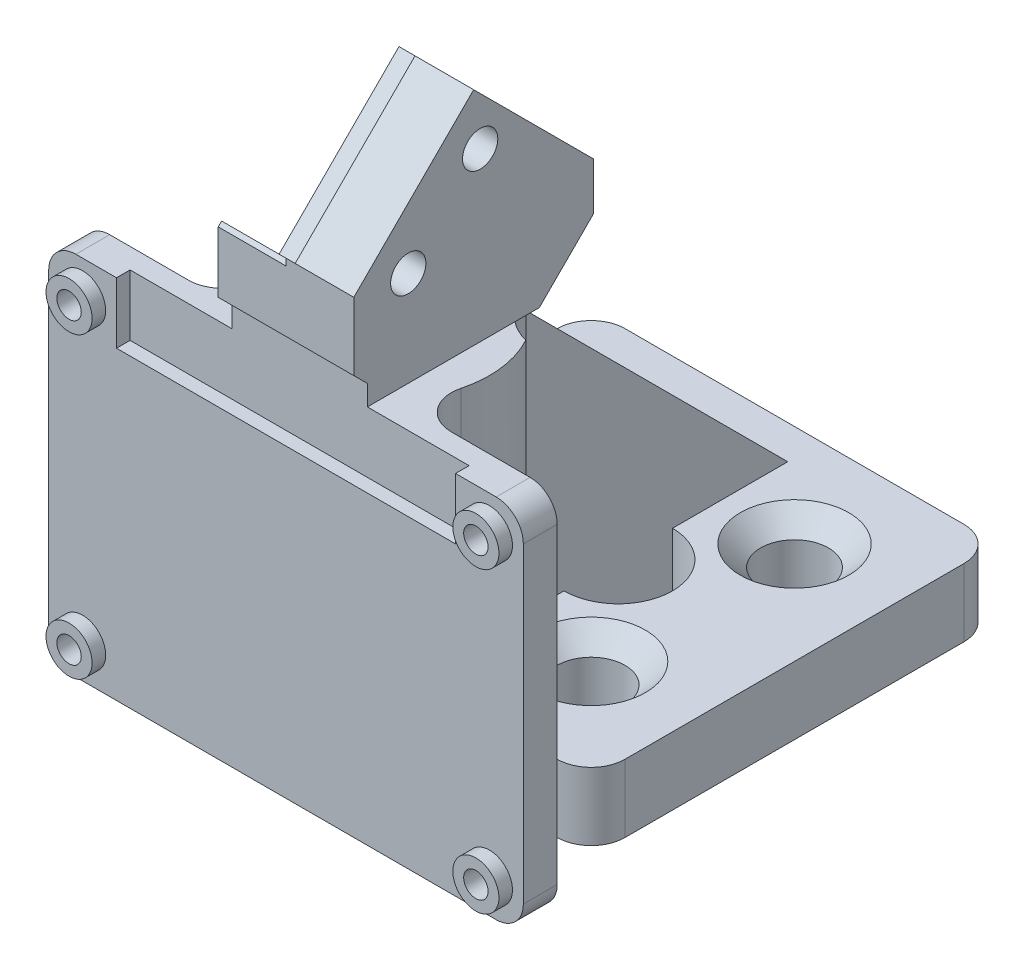
SolidWorks part; units mm, degrees
ref_plane "Front Plane" through (0, 0, 0) normal (0, 0, 1) x (1, 0, 0)
ref_plane "Top Plane" through (0, 0, 0) normal (0, 1, 0) x (1, 0, 0)
ref_plane "Right Plane" through (0, 0, 0) normal (1, 0, 0) x (0, 0, -1)
sketch "Sketch1" plane through (0, 0, 0) normal (0, 1, 0) x (1, 0, 0)
  circle A0 centre (0, 0) radius 15
  dimension "D1" = 30
extrude "Boss-Extrude1" add sketch "Sketch1" along normal blind 54
sketch "Sketch2" plane through (0, 0, 0) normal (1, 0, 0) x (0, 0, -1)
  line L0 (15, 54) -> (-15, 54) construction
  line L1 (-15, 54) -> (20.3553, 54)
  line L2 (-15, 54) -> (-15, 69)
  line L4 (20.3553, 54) -> (20.3553, 69)
  line L5 (-15, 69) -> (2.6777, 86.6777)
  line L6 (2.6777, 86.6777) -> (20.3553, 69)
  point P6 (0, 100)
  dimension "D1" = 25
  dimension "D2" = 15
  dimension "D3" = 15
  dimension "D4" = 45
  dimension "D5" = 15
extrude "Boss-Extrude2" add sketch "Sketch2" along normal mid plane 20
sketch "Sketch4" plane through (0, 42, 42) normal (0, 0.7071, 0.7071) x (1, 0, 0)
  line L0 (10, 38.1838) -> (-10, 38.1838) construction
  line L1 (-12.7, 38.1838) -> (0, 38.1838)
  line L2 (-12.7, 38.1838) -> (-12.7, 63.1838)
  line L3 (-12.7, 63.1838) -> (0, 63.1838)
  line L4 (0, 38.1838) -> (0, 63.1838)
  line L5 (10, 63.1838) -> (-10, 63.1838) construction
  dimension "D1" = 12.7
extrude "Cut-Extrude2" cut sketch "Sketch4" against normal blind 12.7
chamfer "Chamfer1" distance 1 angle 45 1 edges at (-5, 69, 15) first distance on face at (0, 61.5, 15)
sketch "Sketch5" plane through (0, 0, 0) normal (0, -1, 0) x (1, 0, 0)
  circle A0 centre (0, 0) radius 75
  dimension "D1" = 150
sketch "Sketch6" plane through (10, 0, 0) normal (1, 0, 0) x (0, 0, -1)
  line L0 (2.6777, 86.6777) -> (-15, 69) construction
  line L1 (20.3553, 69) -> (2.6777, 86.6777) construction
  line L2 (3.6323, 78.652) -> (-6.9743, 68.0454) construction
  circle A0 centre (3.6323, 78.652) radius 2.6
  circle A1 centre (-6.9743, 68.0454) radius 2.6
  dimension "D4" = 5.2
  dimension "D1" = 6.35
  dimension "D2" = 15
  dimension "D3" = 5
extrude "Cut-Extrude3" cut sketch "Sketch6" against normal through all
sketch "Sketch7" plane through (0, 0, 15) normal (0, 0, 1) x (1, 0, 0)
  line L0 (-31, 0) -> (31, 0)
  line L1 (-35, 4) -> (-35, 50)
  line L2 (-31, 54) -> (31, 54)
  line L3 (35, 4) -> (35, 50)
  line L4 (10, 54) -> (0, 54) construction
  circle A0 centre (-30, 49) radius 1.8
  circle A1 centre (30, 49) radius 1.8
  circle A2 centre (30, 5) radius 1.8
  circle A3 centre (-30, 5) radius 1.8
  arc A4 (31, 54) -> (35, 50) centre (31, 50) cw
  arc A5 (31, 0) -> (35, 4) centre (31, 4) ccw
  arc A6 (-31, 0) -> (-35, 4) centre (-31, 4) cw
  arc A7 (-35, 50) -> (-31, 54) centre (-31, 50) cw
  circle A8 centre (0, 27) radius 5 construction
  point P4 (30, 5)
  point P5 (30, 49)
  point P6 (-30, 49)
  point P7 (-30, 5)
  dimension "D1" = 3.6
  dimension "D2" = 10
  dimension "D3" = 4
  dimension "D4" = 65
  dimension "D5" = 30
  dimension "D6" = 30
  dimension "D7" = 5
  dimension "D8" = 49
  dimension "D9" = 22
  dimension "D10" = 22
  dimension "D11" = 5
extrude "Boss-Extrude4" add sketch "Sketch7" against normal blind 5
fillet "Fillet1" radius 5 2 edges at (-11.1803, 27, 10) (11.1803, 27, 10)
sketch "Sketch8" plane through (0, 0, 0) normal (0, -1, 0) x (1, 0, 0)
  line L1 (30, 0) -> (-30, 0)
  line L2 (30, 0) -> (30, -60)
  line L3 (30, -60) -> (-30, -60)
  line L4 (-30, 0) -> (-30, -60)
  point P4 (0, 0)
  dimension "D1" = 60
  dimension "D2" = 60
extrude "Boss-Extrude5" add sketch "Sketch8" against normal blind 10
sketch "Sketch9" plane through (0, 0, 0) normal (1, 0, 0) x (0, 0, -1)
  line L0 (15, 50) -> (55, 10)
  line L1 (15, 10) -> (15, 54) construction
  line L2 (60, 10) -> (0, 10) construction
  line L3 (15, 50) -> (10, 50)
  line L4 (10, 50) -> (10, 10)
  line L5 (10, 10) -> (55, 10)
  dimension "D1" = 45
  dimension "D2" = 5
  dimension "D3" = 40
extrude "Boss-Extrude6" add sketch "Sketch9" along normal mid plane 8
fillet "Fillet2" radius 5 4 edges at (-30, 5, -60) (30, 5, -60) (-30, 5, 0) (30, 5, 0)
sketch "Sketch10" plane through (0, 10, 0) normal (0, 1, 0) x (1, 0, 0)
  line L0 (-25, 60) -> (25, 60) construction
  line L1 (-15, 45) -> (15, 45) construction
  line L2 (-15, 45) -> (-15, 15) construction
  line L3 (-15, 15) -> (15, 15) construction
  line L4 (15, 45) -> (15, 15) construction
  line L5 (-15, 45) -> (15, 15) construction
  line L6 (-15, 15) -> (15, 45) construction
  circle A0 centre (15, 45) radius 5
  circle A1 centre (-15, 45) radius 5
  circle A2 centre (-15, 15) radius 5
  circle A3 centre (15, 15) radius 5
  point P8 (0, 30)
  dimension "D1" = 10
  dimension "D2" = 30
  dimension "D3" = 30
  dimension "D4" = 30
extrude "Cut-Extrude4" cut sketch "Sketch10" against normal through all
chamfer "Chamfer2" distance 8 angle 45 1 edges at (0, 54, -20.3553)
sketch "Sketch11" plane through (0, 0, 15) normal (0, 0, 1) x (1, 0, 0)
  circle A0 centre (-30, 49) radius 1.8
  circle A1 centre (30, 49) radius 1.8
  circle A2 centre (30, 5) radius 1.8
  circle A3 centre (-30, 5) radius 1.8
  circle A4 centre (-30, 49) radius 1.8 construction
extrude "Extrude-Thin1" add sketch "Sketch11" along normal blind 2 thin thin type one direction wall 1.6
sketch "Sketch12" plane through (0, 0, 15) normal (0, 0, 1) x (1, 0, 0)
  line L0 (-10, 54) -> (-31, 54) construction
  line L1 (-25, 59) -> (25, 59)
  line L2 (-25, 59) -> (-25, 45)
  line L3 (-25, 45) -> (25, 45)
  line L4 (25, 59) -> (25, 45)
  line L5 (-35, 50) -> (-35, 4) construction
  line L6 (35, 4) -> (35, 50) construction
  dimension "D1" = 9
  dimension "D2" = 10
  dimension "D3" = 10
  dimension "D4" = 14
extrude "Cut-Extrude5" cut sketch "Sketch12" against normal blind 2
chamfer "Chamfer3" distance 2 angle 45 1 edges at (0, 59, 13)
sketch "Sketch13" plane through (0, 0, 10) normal (0, 0, -1) x (-1, 0, 0)
  line L649 (-30, 45.8823) -> (-27.3, 47.4412)
  line L650 (-27.3, 47.4412) -> (-27.3, 50.5588)
  line L651 (-27.3, 50.5588) -> (-30, 52.1177)
  line L652 (-30, 52.1177) -> (-32.7, 50.5588)
  line L653 (-32.7, 50.5588) -> (-32.7, 47.4412)
  line L654 (-32.7, 47.4412) -> (-30, 45.8823)
  line L655 (30, 45.8823) -> (32.7, 47.4412)
  line L656 (32.7, 47.4412) -> (32.7, 50.5588)
  line L657 (32.7, 50.5588) -> (30, 52.1177)
  line L658 (30, 52.1177) -> (27.3, 50.5588)
  line L659 (27.3, 50.5588) -> (27.3, 47.4412)
  line L660 (27.3, 47.4412) -> (30, 45.8823)
  line L662 (27.3, 6.5588) -> (27.3, 3.4412)
  line L663 (27.3, 3.4412) -> (30, 1.8823)
  line L664 (30, 1.8823) -> (32.7, 3.4412)
  line L665 (32.7, 3.4412) -> (32.7, 6.5588)
  line L666 (32.7, 6.5588) -> (30, 8.1177)
  line L667 (30, 8.1177) -> (27.3, 6.5588)
  line L668 (-32.7, 6.5588) -> (-32.7, 3.4412)
  line L669 (-32.7, 3.4412) -> (-30, 1.8823)
  line L670 (-30, 1.8823) -> (-27.3, 3.4412)
  line L671 (-27.3, 3.4412) -> (-27.3, 6.5588)
  line L672 (-27.3, 6.5588) -> (-30, 8.1177)
  line L673 (-30, 8.1177) -> (-32.7, 6.5588)
  circle A0 centre (-30, 49) radius 2.7 construction
  circle A1 centre (30, 49) radius 2.7 construction
  circle A2 centre (30, 5) radius 2.7 construction
  circle A3 centre (-30, 5) radius 2.7 construction
  circle A4 centre (-30, 49) radius 1.8 construction
  circle A5 centre (30, 49) radius 1.8 construction
  circle A8 centre (-30, 5) radius 1.8 construction
  circle A9 centre (30, 5) radius 1.8 construction
  dimension "D1" = 5.4
  dimension "D2" = 5.4
  dimension "D3" = 5.4
  dimension "D4" = 5.4
extrude "Cut-Extrude6" cut sketch "Sketch13" against normal blind 2
sketch "Sketch14" plane through (0, 10, 0) normal (0, 1, 0) x (1, 0, 0)
  circle A0 centre (15, 15) radius 8
  circle A1 centre (-15, 15) radius 8
  circle A2 centre (15, 15) radius 5 construction
  dimension "D1" = 16
extrude "Cut-Extrude7" cut sketch "Sketch14" along normal up to surface (44 mm away) up to face at (20.8063, 54, 8.6403)
chamfer "Chamfer4" distance 3 angle 45 4 edges at (-15, 10, -40) (15, 10, -40) (15, 10, -10) (-15, 10, -10)
sketch "Sketch15" plane through (0, 10, 0) normal (0, 1, 0) x (1, 0, 0)
  line L0 (4, 14.4568) -> (4, 55) construction
  line L1 (4, 22) -> (4, 38)
  line L2 (-25, 60) -> (25, 60) construction
  arc A0 (4, 22) -> (4, 38) centre (4, 30) ccw
  dimension "D1" = 8
  dimension "D2" = 30
extrude "Cut-Extrude8" cut sketch "Sketch15" against normal through all
sketch "Sketch16" [suppressed] plane through (0, 42, 42) normal (0, 0.7071, 0.7071) x (1, 0, 0)
  line L1 (10, 63.1838) -> (-10, 63.1838)
  line L2 (10, 63.1838) -> (10, 31.1838)
  line L3 (10, 31.1838) -> (-10, 31.1838)
  line L4 (-10, 63.1838) -> (-10, 31.1838)
  dimension "D1" = 32
extrude "Cut-Extrude9" [suppressed] cut sketch "Sketch16" against normal blind 5.8
sketch "Sketch17" [suppressed] plane through (-10, 0, 0) normal (-1, 0, 0) x (0, 0, 1)
  line L0 (5.4332, 70.3643) -> (0.5542, 65.4853)
  line L1 (10.8988, 64.8988) -> (-6.7789, 82.5765) construction
  line L2 (-11.6579, 77.6974) -> (6.0197, 60.0197) construction
  line L3 (0.5542, 65.4853) -> (9.0395, 57)
  line L4 (9.0395, 57) -> (13, 57)
  line L5 (5.4332, 70.3643) -> (15.8988, 59.8988)
  line L6 (15.8988, 59.8988) -> (13, 57)
  dimension "D1" = 12
extrude "Cut-Extrude10" [suppressed] cut sketch "Sketch17" against normal through all
sketch "Sketch18" [suppressed] plane through (0, 33.0197, 33.0197) normal (0, 0.7071, 0.7071) x (1, 0, 0)
  line L0 (-6.35, 53.1838) -> (-6.35, 63.1838) construction
  line L1 (10, 63.1838) -> (6.7267, 63.1838)
  line L2 (10, 63.1838) -> (10, 53.1838)
  line L3 (10, 53.1838) -> (6.7267, 53.1838)
  line L4 (-22.7, 63.1838) -> (-22.7, 53.1838)
  line L5 (-19.4267, 53.1838) -> (-22.7, 53.1838)
  line L6 (-19.4267, 63.1838) -> (-22.7, 63.1838)
  line L7 (6.7267, 53.1838) -> (-19.4267, 53.1838) construction
  arc A4 (6.7267, 63.1838) -> (-19.4267, 63.1838) centre (-6.35, 58.1838) ccw
  arc A5 (6.7267, 53.1838) -> (-19.4267, 53.1838) centre (-6.35, 58.1838) cw
  point P8 (10, 58.1838)
  point P12 (-6.35, 63.1838)
  point P15 (-6.35, 53.1838)
  dimension "D3" = 14
  dimension "D1" = 5
  dimension "D2" = 32.7
extrude "Boss-Extrude7" [suppressed] add sketch "Sketch18" along normal up to surface (6.9 mm away)
sketch "Sketch19" [suppressed] plane through (0, 20.8223, 20.8223) normal (0, -0.7071, -0.7071) x (1, 0, 0)
  line L0 (10, -46.9203) -> (10, -58.234) construction
  line L1 (-22.7, -63.1838) -> (-22.7, -53.1838) construction
  line L2 (6.25, -55.1838) -> (10, -55.1838)
  line L3 (3.25, -58.1838) -> (3.25, -63.1838)
  line L4 (6.7267, -63.1838) -> (-10, -63.1838) construction
  line L5 (10, -55.1838) -> (10, -63.1838)
  line L6 (10, -63.1838) -> (3.25, -63.1838)
  arc A0 (6.25, -55.1838) -> (3.25, -58.1838) centre (6.25, -58.1838) ccw
  point P4 (-22.7, -58.1838)
  dimension "D2" = 3
  dimension "D1" = 3.75
extrude "Cut-Extrude11" [suppressed] cut sketch "Sketch19" against normal up to surface (17.2497 mm away)
sketch "Sketch20" [suppressed] plane through (0, 33.0197, 33.0197) normal (0, -0.7071, -0.7071) x (1, 0, 0)
  line L0 (6.25, -58.1838) -> (-18.95, -58.1838) construction
  line L1 (-22.7, -63.1838) -> (-22.7, -53.1838) construction
  line L2 (10, -55.1838) -> (10, -63.1838) construction
  circle A0 centre (6.25, -58.1838) radius 1.5
  circle A1 centre (-18.95, -58.1838) radius 1.5
  point P5 (-22.7, -58.1838)
  dimension "D3" = 3
  dimension "D1" = 3.75
  dimension "D2" = 3.75
extrude "Cut-Extrude12" [suppressed] cut sketch "Sketch20" against normal through all
chamfer "Chamfer5" [suppressed] distance 7 angle 45
sketch "Sketch21" [suppressed] plane through (0, 0, 0) normal (0, 0, 1) x (1, 0, 0)
  line L0 (-10, 54) -> (-15, 54)
  line L1 (-15, 54) -> (-23.25, 62.25)
  line L2 (-23.25, 62.25) -> (-23.25, 75.5054)
  line L3 (-23.25, 75.5054) -> (-10, 75.5054)
  line L4 (-10, 54) -> (-10, 75.5054)
  line L5 (-19.4267, 75.5054) -> (-22.7, 75.5054) construction
  dimension "D1" = 45
  dimension "D2" = 13.25
extrude "Boss-Extrude8" [suppressed] add sketch "Sketch21" against normal blind 5
sketch "Sketch22" [suppressed] plane through (0, 33.0197, 33.0197) normal (0, -0.7071, -0.7071) x (1, 0, 0)
  line L0 (-23.25, -56.9259) -> (-23.25, -47.5529) construction
  line L2 (10, -63.1838) -> (10, -49.1838)
  line L3 (10, -49.1838) -> (10.7, -49.1838)
  line L4 (10.7, -63.1838) -> (10.7, -49.1838)
  line L6 (-22.7, -63.1838) -> (-22.7, -53.1838)
  line L7 (-22.7, -53.1838) -> (-23.25, -53.1838)
  line L8 (-23.25, -63.1838) -> (-23.25, -53.1838)
  line L9 (-19.4267, -63.1838) -> (-22.7, -63.1838) construction
  line L10 (-18.25, -63.1838) -> (-22.7, -63.1838)
  line L11 (-18.25, -63.1838) -> (-18.25, -65.1838)
  line L12 (-18.25, -65.1838) -> (-23.25, -65.1838)
  line L13 (-23.25, -63.1838) -> (-23.25, -65.1838)
  line L15 (10, -63.1838) -> (5.7, -63.1838)
  line L16 (10.7, -63.1838) -> (10.7, -65.1838)
  line L17 (10.7, -65.1838) -> (5.7, -65.1838)
  line L18 (5.7, -63.1838) -> (5.7, -65.1838)
  dimension "D1" = 0.7
  dimension "D2" = 14
  dimension "D3" = 2
  dimension "D4" = 5
extrude "Boss-Extrude9" [suppressed] add sketch "Sketch22" against normal up to surface (6.9 mm away)
sketch "Sketch23" [suppressed] plane through (-23.25, 0, 0) normal (-1, 0, 0) x (0, 0, 1)
  line L0 (-8.1931, 83.9907) -> (-13.0721, 79.1116) construction
  line L1 (-5, 62.25) -> (0, 62.25) construction
  line L2 (-11.6579, 77.6974) -> (-6.7789, 82.5765) construction
  line L3 (-5, 71.0395) -> (-13.0721, 79.1116) construction
  line L4 (-18.0219, 84.0614) -> (-13.0721, 79.1116) construction
  line L5 (-8.1931, 83.9907) -> (0.2922, 75.5054) construction
  line L6 (-5, 65.25) -> (0, 65.25) construction
  line L7 (-5, 71.0395) -> (-5, 62.25) construction
  line L8 (0, 75.2132) -> (0, 62.25) construction
  circle A0 centre (-2.5, 65.25) radius 0.75
  circle A1 centre (-9.2184, 80.1369) radius 0.75
  dimension "D3" = 1.5
  dimension "D1" = 2
  dimension "D2" = 3
extrude "Cut-Extrude13" [suppressed] cut sketch "Sketch23" against normal blind 5
sketch "Sketch24" [suppressed] plane through (10.7, 0, 0) normal (1, 0, 0) x (0, 0, -1)
  line L0 (-0.9993, 74.7983) -> (3.8798, 69.9192) construction
  line L1 (13.0721, 79.1116) -> (1.7584, 67.7979) construction
  line L2 (-3.1206, 72.677) -> (8.1931, 83.9907) construction
  line L3 (-3.1206, 72.677) -> (1.7584, 67.7979) construction
  line L4 (6.0718, 81.8693) -> (10.9508, 76.9903) construction
  line L5 (-3.1206, 72.677) -> (8.1931, 83.9907) construction
  line L6 (13.0721, 79.1116) -> (1.7584, 67.7979) construction
  line L7 (8.1931, 83.9907) -> (13.0721, 79.1116) construction
  circle A0 centre (1.4402, 72.3588) radius 0.75
  circle A1 centre (8.5113, 79.4298) radius 0.75
  dimension "D2" = 1.5
  dimension "D1" = 3
  dimension "D3" = 3
extrude "Cut-Extrude14" [suppressed] cut sketch "Sketch24" against normal blind 5
sketch "Sketch25" [suppressed] plane through (0, 0, -20.3553) normal (0, 0, -1) x (-1, 0, 0)
  line L0 (3.375, 62) -> (3.375, 69) construction
  line L1 (-3.25, 62) -> (10, 62) construction
  line L2 (-3.25, 69) -> (10, 69) construction
  circle A0 centre (3.375, 65.5) radius 0.75
  dimension "D1" = 1.5
extrude "Cut-Extrude15" [suppressed] cut sketch "Sketch25" against normal blind 5
sketch "Sketch26" plane through (0, 33.0197, 33.0197) normal (0, 0.7071, 0.7071) x (1, 0, 0)
  line L0 (0, 60.7838) -> (0, 55.5838) construction
  line L1 (0, 45.7838) -> (0, 40.5838) construction
  line L3 (0, 38.1838) -> (0, 63.1838) construction
  circle A0 centre (-5, 58.1838) radius 2.5
  circle A1 centre (-5, 43.1838) radius 2.5
  point P5 (0, 58.1838)
  point P8 (0, 43.1838)
  dimension "D1" = 5
  dimension "D2" = 5
extrude "Cut-Extrude16" cut sketch "Sketch26" against normal blind 37
sketch "Sketch27" plane through (-10, 0, 0) normal (-1, 0, 0) x (0, 0, 1)
  line L0 (-20.3553, 62) -> (-6.1777, 47.8223)
  line L1 (-6.1777, 47.8223) -> (-27.3909, 26.6091)
  line L2 (-27.3909, 26.6091) -> (-41.5685, 40.7868)
  line L3 (-41.5685, 40.7868) -> (-20.3553, 62)
  line L4 (6.0197, 60.0197) -> (-6.1777, 47.8223) construction
  line L5 (-20.3553, 62) -> (-12.3553, 54) construction
  dimension "D1" = 30
extrude "Cut-Extrude17" cut sketch "Sketch27" against normal blind 9
chamfer "Chamfer6" distance 3 angle 45 1 edges at (-4, 29.3591, -30.1409)
sketch "Sketch29" plane through (0, 42, 42) normal (0, 0.7071, 0.7071) x (1, 0, 0)
  line L0 (10, 63.1838) -> (0, 63.1838) construction
  line L1 (0, 38.1838) -> (1.35, 38.1838)
  line L2 (0, 38.1838) -> (0, 63.1838)
  line L3 (0, 63.1838) -> (1.35, 63.1838)
  line L4 (1.35, 38.1838) -> (1.35, 63.1838)
  line L5 (10, 38.1838) -> (0, 38.1838) construction
extrude "Cut-Extrude18" cut sketch "Sketch29" against normal blind 12.7
